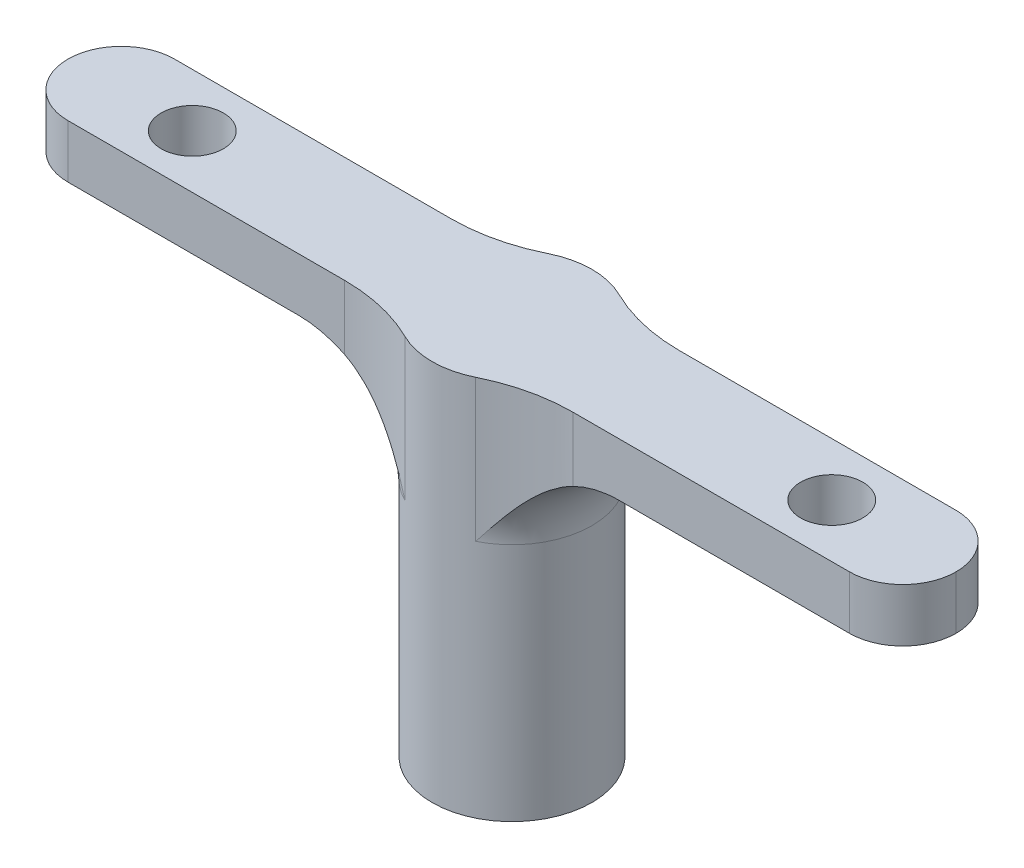
SolidWorks part; units mm, degrees
ref_plane "Front Plane" through (0, 0, 0) normal (0, 0, 1) x (1, 0, 0)
ref_plane "Top Plane" through (0, 0, 0) normal (0, 1, 0) x (1, 0, 0)
ref_plane "Right Plane" through (0, 0, 0) normal (1, 0, 0) x (0, 0, -1)
sketch "Sketch1" plane through (0, 0, 0) normal (0, 1, 0) x (1, 0, 0)
  line L0 (0, -3) -> (0, -4.5)
  circle A0 centre (0, 0) radius 3
  circle A1 centre (0, 0) radius 4.5
  dimension "D1" = 6
  dimension "D2" = 1.5
extrude "Boss-Extrude1" add sketch "Sketch1" along normal blind 18.5 contours A1 A0 region at (-3.092, 0, -3.092)
sketch "Sketch2" plane through (0, 18.5, 0) normal (0, 1, 0) x (1, 0, 0)
  line L0 (0, 0) -> (0, 3) construction
  line L1 (0, 0) -> (0, -3) construction
  line L2 (25, 3) -> (25, -3)
  line L3 (25, 3) -> (-25, 3)
  line L4 (0, 3) -> (0, -3)
  line L5 (25, -3) -> (-25, -3)
  line L6 (-25, 3) -> (-25, -3)
  circle A0 centre (0, 0) radius 4.5 construction
  circle A1 centre (0, 0) radius 4.5
  circle A2 centre (0, 0) radius 3 construction
  circle M9 centre (0, 0) radius 4.5
  circle M10 centre (0, 0) radius 3
  dimension "D1" = 25
extrude "Boss-Extrude2" add sketch "Sketch2" along normal blind 3 contours L3 L6 L5 M9 | L5 L2 L3 M9 | L5 L3 M9 M10 | L4 M10 | L4 M10 | L5 L3 M10 M9 | L5 M9 | L3 M9 region at (14.5673, 18.5, 0) region at (3.1536, 18.5, 0) region at (0, 18.5, -3.6095) region at (0, 18.5, 3.6095) region at (-3.1536, 18.5, 0) region at (1.2732, 18.5, 0) region at (-1.2732, 18.5, 0) region at (-14.5673, 18.5, 0)
fillet "Fillet1" radius 3 4 edges at (-25, 20, 3) (-25, 20, -3) (25, 20, 3) (25, 20, -3)
fillet "Fillet2" radius 5 2 edges at (-4.5, 18.5, 0) (4.5, 18.5, 0)
fillet "Fillet3" radius 10 4 edges at (3.3541, 17.5, -3) (3.3541, 17.5, 3) (-3.3541, 17.5, 3) (-3.3541, 17.5, -3)
sketch "Sketch4" plane through (0, 21.5, 0) normal (0, 1, 0) x (1, 0, 0)
  line L0 (0, 0) -> (18, 0)
  line L1 (0, 0) -> (0, -2.8802) construction
  circle A0 centre (18, 0) radius 1.75
  circle A1 centre (-18, 0) radius 1.75
  dimension "D2" = 3.5
  dimension "D1" = 18
extrude "Cut-Extrude1" cut sketch "Sketch4" against normal through all contours A1 | A0 region at (18, 21.5, 1.7005) region at (-18, 21.5, 0)
